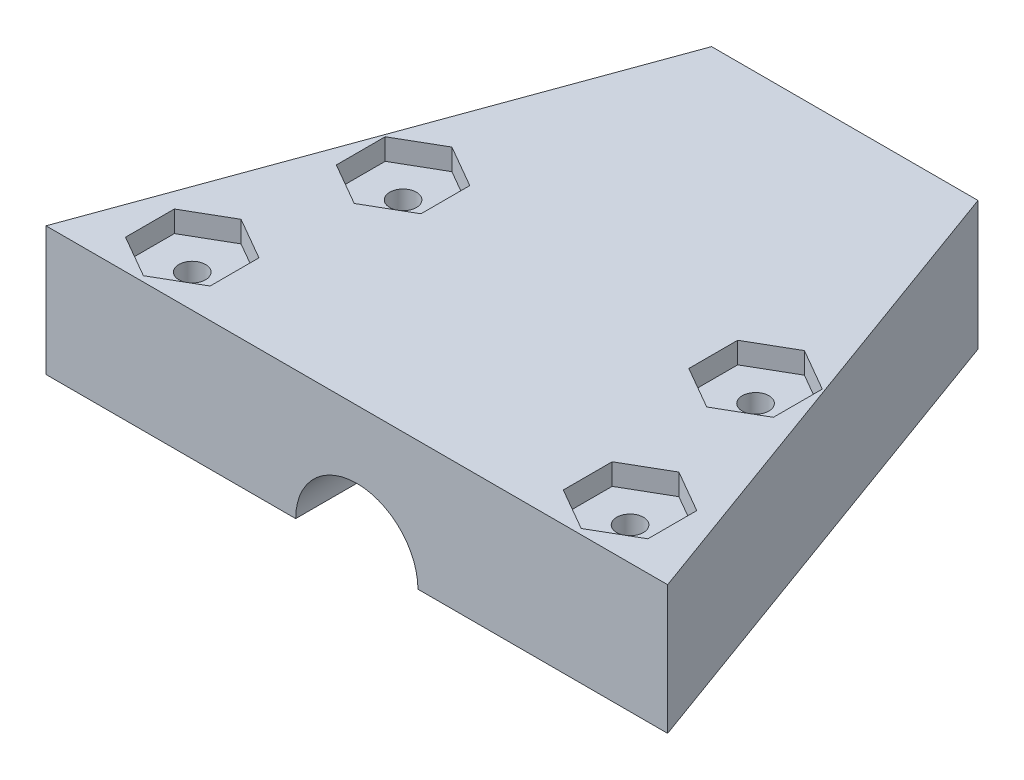
SolidWorks part; units mm, degrees
ref_plane "Front Plane" through (0, 0, 0) normal (0, 0, 1) x (1, 0, 0)
ref_plane "Top Plane" through (0, 0, 0) normal (0, 1, 0) x (1, 0, 0)
ref_plane "Right Plane" through (0, 0, 0) normal (1, 0, 0) x (0, 0, -1)
sketch "Sketch6" plane through (0, 0, 0) normal (0, 1, 0) x (1, 0, 0)
  line L0 (-16.8369, 5.7834) -> (13.1631, 5.7834)
  line L1 (13.1631, 5.7834) -> (33.1631, -49.1662)
  line L2 (33.1631, -49.1662) -> (-36.8369, -49.1662)
  line L3 (-36.8369, -49.1662) -> (-16.8369, 5.7834)
  circle A0 centre (13.1631, -5.2166) radius 1.78
  circle A1 centre (-16.8369, -5.2166) radius 1.78
  circle A2 centre (-26.4869, -43.0491) radius 1.78
  circle A3 centre (22.8131, -43.0491) radius 1.78
  dimension "D1" = 3.56
  dimension "D3" = 3.56
  dimension "D4" = 3.56
  dimension "D5" = 3.56
  dimension "D2" = 70
  dimension "D6" = 30
  dimension "D7" = 11
  dimension "D8" = 11
  dimension "D9" = 49.3
  dimension "D10" = 10.35
  dimension "D11" = 10.35
  dimension "D12" = 30
extrude "Boss-Extrude3" add sketch "Sketch6" along normal blind 14.5 contours L3 L0 L1 L2
sketch "Sketch8" plane through (0, 0, 49.1662) normal (0, 0, 1) x (1, 0, 0)
  line L0 (33.1631, 0) -> (-36.8369, 0) construction
  circle A0 centre (-1.8369, 0) radius 6.8846
extrude "Cut-Extrude3" cut sketch "Sketch8" against normal blind 88
sketch "Sketch9" plane through (0, 14.5, 0) normal (0, 1, 0) x (1, 0, 0)
  line L1 (-21.6619, -29.6329) -> (-16.8988, -26.8829)
  line L2 (-16.8988, -26.8829) -> (-16.8988, -21.3829)
  line L3 (-16.8988, -21.3829) -> (-21.6619, -18.6329)
  line L4 (-21.6619, -18.6329) -> (-26.4251, -21.3829)
  line L5 (-26.4251, -21.3829) -> (-26.4251, -26.8829)
  line L6 (-26.4251, -26.8829) -> (-21.6619, -29.6329)
  line L7 (-26.4869, -48.5491) -> (-21.7238, -45.7991)
  line L8 (-21.7238, -45.7991) -> (-21.7238, -40.2991)
  line L9 (-21.7238, -40.2991) -> (-26.4869, -37.5491)
  line L10 (-26.4869, -37.5491) -> (-31.2501, -40.2991)
  line L11 (-31.2501, -40.2991) -> (-31.2501, -45.7991)
  line L12 (-31.2501, -45.7991) -> (-26.4869, -48.5491)
  line L13 (22.8131, -48.5491) -> (27.5762, -45.7991)
  line L14 (27.5762, -45.7991) -> (27.5762, -40.2991)
  line L15 (27.5762, -40.2991) -> (22.8131, -37.5491)
  line L16 (22.8131, -37.5491) -> (18.0499, -40.2991)
  line L17 (18.0499, -40.2991) -> (18.0499, -45.7991)
  line L18 (18.0499, -45.7991) -> (22.8131, -48.5491)
  line L19 (18.0315, -29.6329) -> (22.7946, -26.8829)
  line L20 (22.7946, -26.8829) -> (22.7946, -21.3829)
  line L21 (22.7946, -21.3829) -> (18.0315, -18.6329)
  line L22 (18.0315, -18.6329) -> (13.2683, -21.3829)
  line L23 (13.2683, -21.3829) -> (13.2683, -26.8829)
  line L24 (13.2683, -26.8829) -> (18.0315, -29.6329)
  circle A0 centre (-21.6619, -24.1329) radius 4.7631 construction
  circle A1 centre (-26.4869, -43.0491) radius 4.7631 construction
  circle A2 centre (22.8131, -43.0491) radius 4.7631 construction
  circle A3 centre (18.0315, -24.1329) radius 4.7631 construction
  point P0 (-16.8369, -5.2166)
  point P1 (13.1631, -5.2166)
  point P3 (22.8131, -43.0491)
  point P5 (-26.4869, -43.0491)
  point P7 (18.0315, -24.1329)
  point P9 (-21.6619, -24.1329)
  dimension "D1" = 5.5
  dimension "D2" = 5.5
  dimension "D3" = 5.5
  dimension "D4" = 5.5
extrude "Cut-Extrude4" cut sketch "Sketch9" against normal blind 2.4
sketch "Sketch10" plane through (0, 0, 0) normal (0, -1, 0) x (1, 0, 0)
  line L1 (-26.4869, 37.5491) -> (-21.7238, 40.2991)
  line L2 (-21.7238, 40.2991) -> (-21.7238, 45.7991)
  line L3 (-21.7238, 45.7991) -> (-26.4869, 48.5491)
  line L4 (-26.4869, 48.5491) -> (-31.2501, 45.7991)
  line L5 (-31.2501, 45.7991) -> (-31.2501, 40.2991)
  line L6 (-31.2501, 40.2991) -> (-26.4869, 37.5491)
  line L7 (-21.6619, 18.6329) -> (-16.8988, 21.3829)
  line L8 (-16.8988, 21.3829) -> (-16.8988, 26.8829)
  line L9 (-16.8988, 26.8829) -> (-21.6619, 29.6329)
  line L10 (-21.6619, 29.6329) -> (-26.4251, 26.8829)
  line L11 (-26.4251, 26.8829) -> (-26.4251, 21.3829)
  line L12 (-26.4251, 21.3829) -> (-21.6619, 18.6329)
  line L13 (18.0315, 18.6329) -> (22.7946, 21.3829)
  line L14 (22.7946, 21.3829) -> (22.7946, 26.8829)
  line L15 (22.7946, 26.8829) -> (18.0315, 29.6329)
  line L16 (18.0315, 29.6329) -> (13.2683, 26.8829)
  line L17 (13.2683, 26.8829) -> (13.2683, 21.3829)
  line L18 (13.2683, 21.3829) -> (18.0315, 18.6329)
  line L19 (22.8131, 37.5491) -> (27.5762, 40.2991)
  line L20 (27.5762, 40.2991) -> (27.5762, 45.7991)
  line L21 (27.5762, 45.7991) -> (22.8131, 48.5491)
  line L22 (22.8131, 48.5491) -> (18.0499, 45.7991)
  line L23 (18.0499, 45.7991) -> (18.0499, 40.2991)
  line L24 (18.0499, 40.2991) -> (22.8131, 37.5491)
  circle A0 centre (-26.4869, 43.0491) radius 4.7631 construction
  circle A1 centre (-21.6619, 24.1329) radius 4.7631 construction
  circle A2 centre (18.0315, 24.1329) radius 4.7631 construction
  circle A3 centre (22.8131, 43.0491) radius 4.7631 construction
extrude "Cut-Extrude5" cut sketch "Sketch10" against normal blind 2.4
hole_wizard "#39 (0.11811024) Diameter Hole1" positions "3DSketch1" profile "Sketch11" hole size "#39" standard "ANSI Inch" end condition through all
sketch3d "3DSketch1"
  point P0 (-21.6619, 14.5, 24.1329)
  point P3 (18.0315, 14.5, 24.1329)
  point P6 (-26.4869, 14.5, 43.0491)
  point P9 (22.8131, 14.5, 43.0491)
sketch "Sketch11" plane through (-21.6619, 14.5, 24.1329) normal (1, 0, 0) x (0, 0, 1)
  line L0 (0, 0) -> (0, 14.5)
  line L1 (0, 14.5) -> (1.5, 14.5)
  line L2 (1.5, 14.5) -> (1.5, 0)
  line L5 (1.5, 0) -> (0, 0)
  line L11 (0, -6.35) -> (0, 107.95) construction
  dimension "Thru Hole Dia." = 3
  dimension "Thru Hole Depth" = 14.5
